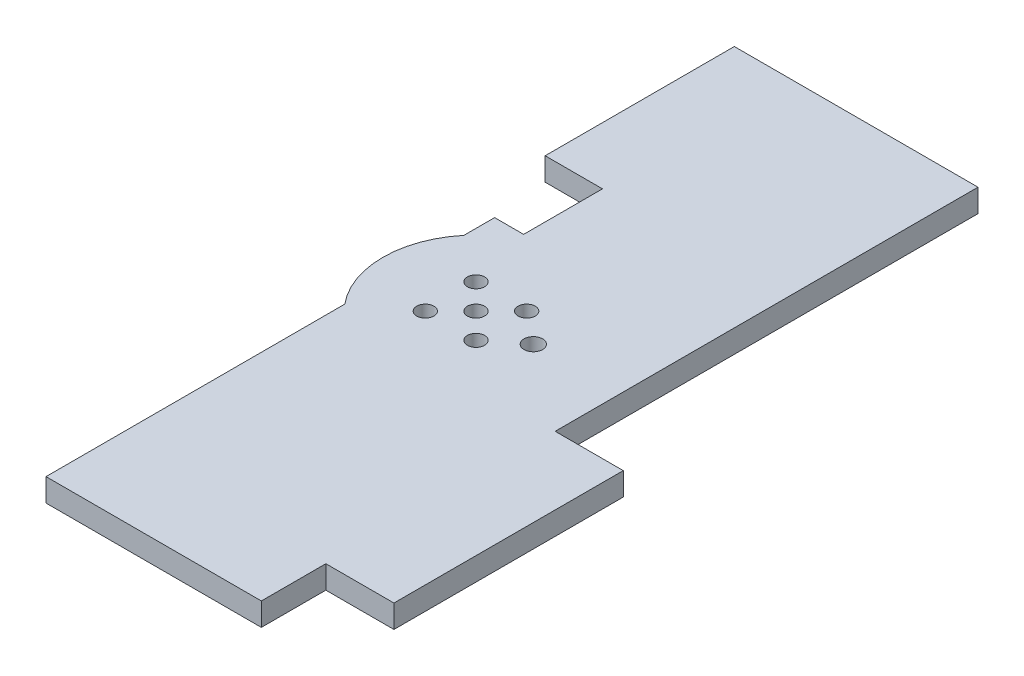
SolidWorks part; units mm, degrees
ref_plane "Front Plane" through (0, 0, 0) normal (0, 0, 1) x (1, 0, 0)
ref_plane "Top Plane" through (0, 0, 0) normal (0, 1, 0) x (1, 0, 0)
ref_plane "Right Plane" through (0, 0, 0) normal (1, 0, 0) x (0, 0, -1)
sketch "Sketch1" plane through (0, 0, 0) normal (0, 1, 0) x (1, 0, 0)
  line L0 (0, 25) -> (15, 25)
  line L1 (15, 25) -> (15, -4.5)
  line L2 (-0.025, -25) -> (-0.025, -4.1533)
  line L3 (15, -25) -> (-0.025, -25)
  line L4 (0, 25) -> (-2, 25)
  line L5 (-2, 25) -> (-2, 11.8)
  line L6 (15, -20.5) -> (19.75, -20.5)
  line L7 (0, 0) -> (160.2024, 0) construction
  line L8 (-2, 11.8) -> (2, 11.8)
  line L9 (2, 11.8) -> (2, 6.3)
  line L10 (2, 6.3) -> (-0.025, 6.3)
  line L11 (19.75, -20.5) -> (19.75, -4.5)
  line L12 (19.75, -4.5) -> (15, -4.5)
  line L14 (-0.025, 4.1533) -> (-0.025, 6.3)
  line L15 (15, -20.5) -> (15, -25)
  arc A0 (-0.025, 4.1533) -> (-0.025, -4.1533) centre (4.975, 0) ccw
  point P16 (0, 0)
  dimension "D6" = 17
  dimension "D10" = 13
  dimension "D1" = 15
  dimension "D2" = 50
  dimension "D3" = 13
  dimension "D4" = 13.2
  dimension "D5" = 5.5
  dimension "D7" = 4.5
  dimension "D8" = 16
  dimension "D9" = 4.75
  dimension "D11" = 5
extrude "Boss-Extrude1" add sketch "Sketch1" along normal blind 1.6 contours L2 A0 L14 L10 L9 L8 L5 L4 L0 L1 L12 L11 L6 L15 L3
sketch "Sketch3" plane through (0, 1.6, 0) normal (0, 1, 0) x (1, 0, 0)
  line L0 (3.2072, 1.7678) -> (6.7427, -1.7678) construction
  line L1 (3.2072, -1.7678) -> (6.7427, 1.7678) construction
  line L3 (-0.025, -25) -> (-0.025, -4.1533) construction
  circle A0 centre (4.975, 0) radius 0.6
  circle A1 centre (4.975, 0) radius 2.5 construction
  circle A2 centre (3.2072, 1.7678) radius 0.6
  circle A3 centre (6.7427, 1.7678) radius 0.6
  circle A4 centre (6.7427, -1.7678) radius 0.6
  circle A5 centre (3.2072, -1.7678) radius 0.6
  circle A6 centre (8.975, 0) radius 0.65
  dimension "D1" = 1.2
  dimension "D2" = 1.3
  dimension "D5" = 5
  dimension "D3" = 4
  dimension "D4" = 5
extrude "M12 mounting holes" cut sketch "Sketch3" against normal up to next
